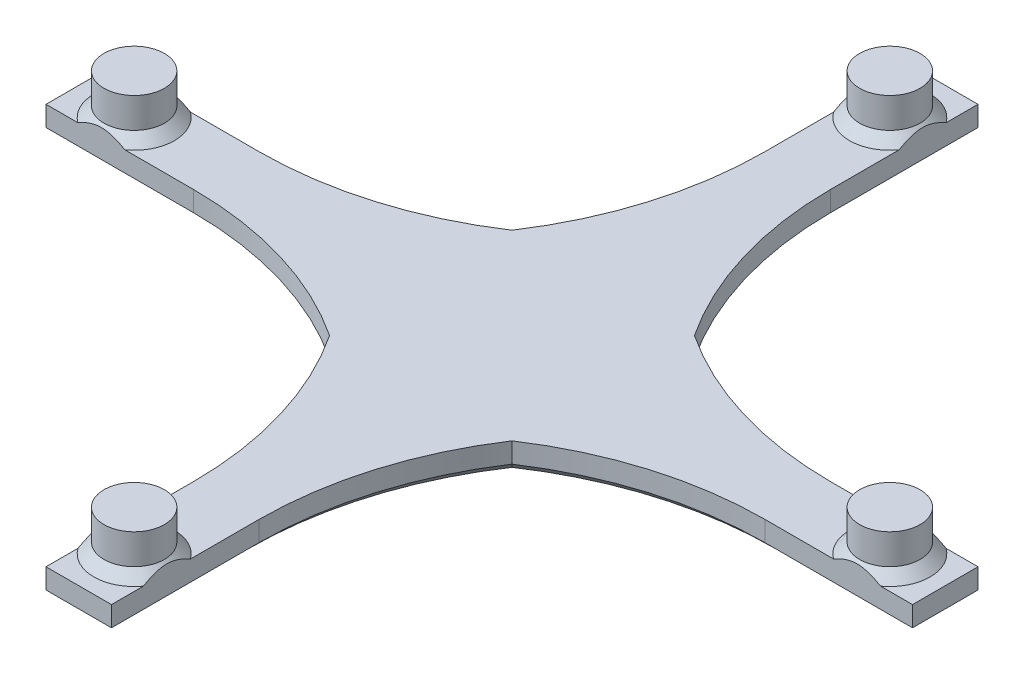
SolidWorks part; units mm, degrees
material "ABS"
ref_plane "Front Plane" through (0, 0, 0) normal (0, 0, 1) x (1, 0, 0)
ref_plane "Top Plane" through (0, 0, 0) normal (0, 1, 0) x (1, 0, 0)
ref_plane "Right Plane" through (0, 0, 0) normal (1, 0, 0) x (0, 0, -1)
sketch "Sketch1" plane through (0, 0, 0) normal (0, 1, 0) x (1, 0, 0)
  circle A0 centre (0, 0) radius 3
  dimension "D1" = 6
extrude "Boss-Extrude1" add sketch "Sketch1" against normal blind 4
sketch "Sketch2" plane through (0, 0, 0) normal (0, 1, 0) x (1, 0, 0)
  line L0 (-3.25, 43) -> (-3.25, 13.8566)
  line L1 (-43, -43) -> (43, -43) construction
  line L2 (-43, -43) -> (-43, 43) construction
  line L3 (-43, 43) -> (43, 43) construction
  line L4 (43, -43) -> (43, 43) construction
  line L5 (-43, -43) -> (43, 43) construction
  line L6 (-43, 43) -> (43, -43) construction
  line L7 (-3.25, 13.8566) -> (-13.8566, 3.25)
  line L8 (-13.8566, 3.25) -> (-43, 3.25)
  line L9 (-43, 3.25) -> (-43, -3.25)
  line L10 (-43, -3.25) -> (-13.8566, -3.25)
  line L11 (-13.8566, -3.25) -> (-3.25, -13.8566)
  line L12 (-3.25, -13.8566) -> (-3.25, -43)
  line L13 (-3.25, -43) -> (3.25, -43)
  line L14 (3.25, -43) -> (3.25, -13.8566)
  line L15 (3.25, -13.8566) -> (13.8566, -3.25)
  line L16 (13.8566, -3.25) -> (43, -3.25)
  line L17 (43, -3.25) -> (43, 3.25)
  line L18 (43, 3.25) -> (13.8566, 3.25)
  line L19 (13.8566, 3.25) -> (3.25, 13.8566)
  line L20 (3.25, 13.8566) -> (3.25, 43)
  line L21 (3.25, 43) -> (-3.25, 43)
  point P0 (0, 0)
  point P19 (0, 43)
  point P23 (0, -43)
  point P24 (-43, 0)
  point P25 (43, 0)
  point P26 (0, 0)
  point P27 (0, 0)
  point P28 (0, 0)
  point P29 (-4.4141, -9.4188)
  point P30 (3.25, -18.6201)
  dimension "D1" = 6.5
  dimension "D2" = 15
  dimension "D3" = 86
extrude "Boss-Extrude2" add sketch "Sketch2" along normal blind 3
sketch "Sketch3" plane through (0, 3, 0) normal (0, 1, 0) x (1, 0, 0)
  line L0 (0, 37.5) -> (0, -37.5) construction
  line L1 (37.5, 0) -> (-37.5, 0) construction
  circle A0 centre (-37.5, 0) radius 3
  circle A1 centre (0, 37.5) radius 3
  circle A2 centre (37.5, 0) radius 3
  circle A3 centre (0, -37.5) radius 3
  point P8 (0, 0)
  point P9 (0, 0)
  dimension "D1" = 6
  dimension "D2" = 75
extrude "Boss-Extrude3" add sketch "Sketch3" along normal blind 4
fillet "Fillet2" radius 35 8 edges at (-13.8566, 1.5, -3.25) (-3.25, 1.5, -13.8566) (3.25, 1.5, -13.8566) (13.8566, 1.5, -3.25) (13.8566, 1.5, 3.25) (3.25, 1.5, 13.8566) (-13.8566, 1.5, 3.25) (-3.25, 1.5, 13.8566)
chamfer "Chamfer1" distance 1 angle 45 4 edges at (-37.5, 3, 3) (37.5, 3, 3) (0, 3, 40.5) (0, 3, -34.5)
chamfer "Chamfer2" distance 1 angle 45 20 edges at (-35.677, 0, -3.25) (-18.2768, 0, -4.7321) (-4.7321, 0, -18.2768) (-3.25, 0, -35.677) (3.25, 0, -35.677) (4.7321, 0, -18.2768) (18.2768, 0, -4.7321) (35.677, 0, -3.25) (35.677, 0, 3.25) (18.2768, 0, 4.7321) (4.7321, 0, 18.2768) (3.25, 0, 35.677) (-3.25, 0, 35.677) (-4.7321, 0, 18.2768) (-18.2768, 0, 4.7321) (-35.677, 0, 3.25) (0, 0, -43) (43, 0, 0) (0, 0, 43) (-43, 0, 0)
